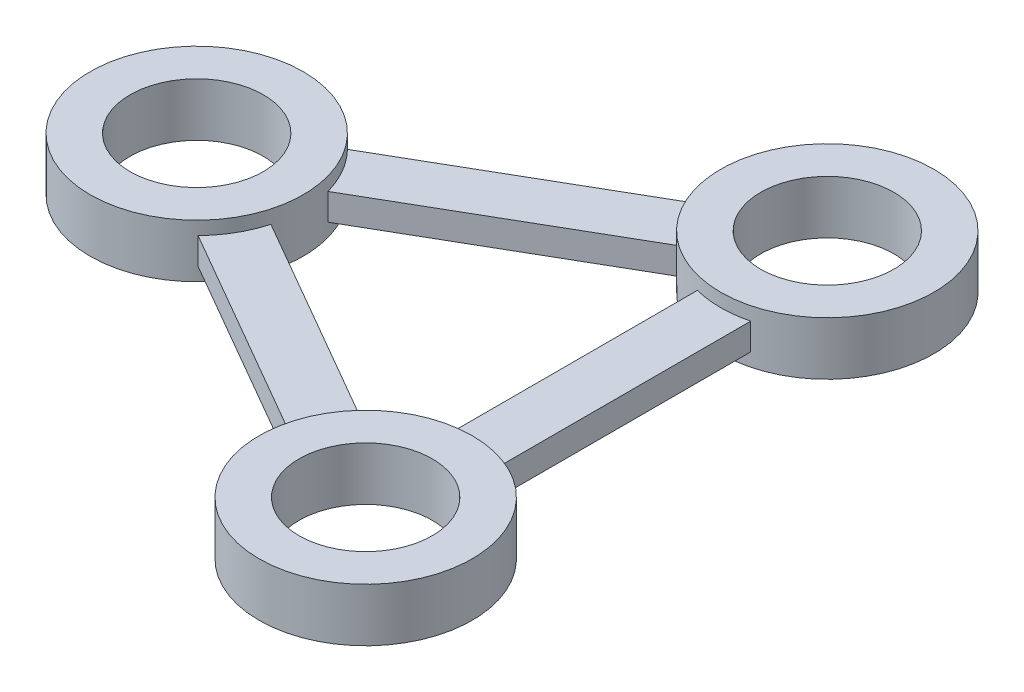
SolidWorks part; units mm, degrees
ref_plane "Front Plane" through (0, 0, 0) normal (0, 0, 1) x (1, 0, 0)
ref_plane "Top Plane" through (0, 0, 0) normal (0, 1, 0) x (1, 0, 0)
ref_plane "Right Plane" through (0, 0, 0) normal (1, 0, 0) x (0, 0, -1)
sketch "Sketch1" plane through (0, 0, 0) normal (0, 1, 0) x (1, 0, 0)
  line L9 (-121.4586, -58.5752) -> (-38.5412, -10.7042)
  line L10 (-111.4588, -75.8958) -> (-28.5414, -28.0248)
  line L11 (0, 0) -> (0, -173.2) construction
  line L12 (-150, -86.6) -> (0, 0) construction
  line L13 (-38.5412, -162.4958) -> (-121.4586, -114.6248)
  line L14 (-28.5414, -145.1752) -> (-111.4588, -97.3042)
  line L15 (-150, -86.6) -> (0, -173.2) construction
  line L17 (10, -38.7298) -> (10, -134.4702)
  line L18 (-10, -38.7298) -> (-10, -134.4702)
  circle A0 centre (0, 0) radius 40
  circle A1 centre (0, -173.2) radius 40
  circle A2 centre (-150, -86.6) radius 40
  circle A3 centre (0, 0) radius 25
  circle A4 centre (0, -173.2) radius 25
  circle A5 centre (-150, -86.6) radius 25
  point P10 (-75, -129.9)
  dimension "D1" = 80
  dimension "D2" = 80
  dimension "D3" = 80
  dimension "D4" = 150
  dimension "D5" = 150
  dimension "D6" = 86.6
  dimension "D7" = 86.6
  dimension "D8" = 50
  dimension "D9" = 50
  dimension "D10" = 50
  dimension "D11" = 20
  dimension "D12" = 10
  dimension "D13" = 20
  dimension "D14" = 10
  dimension "D15" = 10
  dimension "D16" = 20
extrude "Boss-Extrude1" add sketch "Sketch1" along normal mid plane 20 contours A1 A4 | A2 A5 | A0 A3 region at (-116.3385, 0, 67.1661) region at (-5.2488, 0, -38.5126) region at (-33.6615, 0, 153.7661)
extrude "Boss-Extrude2" add sketch "Sketch1<3>" along normal mid plane 10 contours A1 L17 A0 L18 | A2 L13 A1 L14 | A2 L10 A0 L9 region at (-75, 0, 43.3) region at (-75, 0, 129.9) region at (0, 0, 86.6)
sketch "Sketch1<3>" plane through (0, 0, 0) normal (0, 1, 0) x (1, 0, 0) same geometry as "Sketch1"
